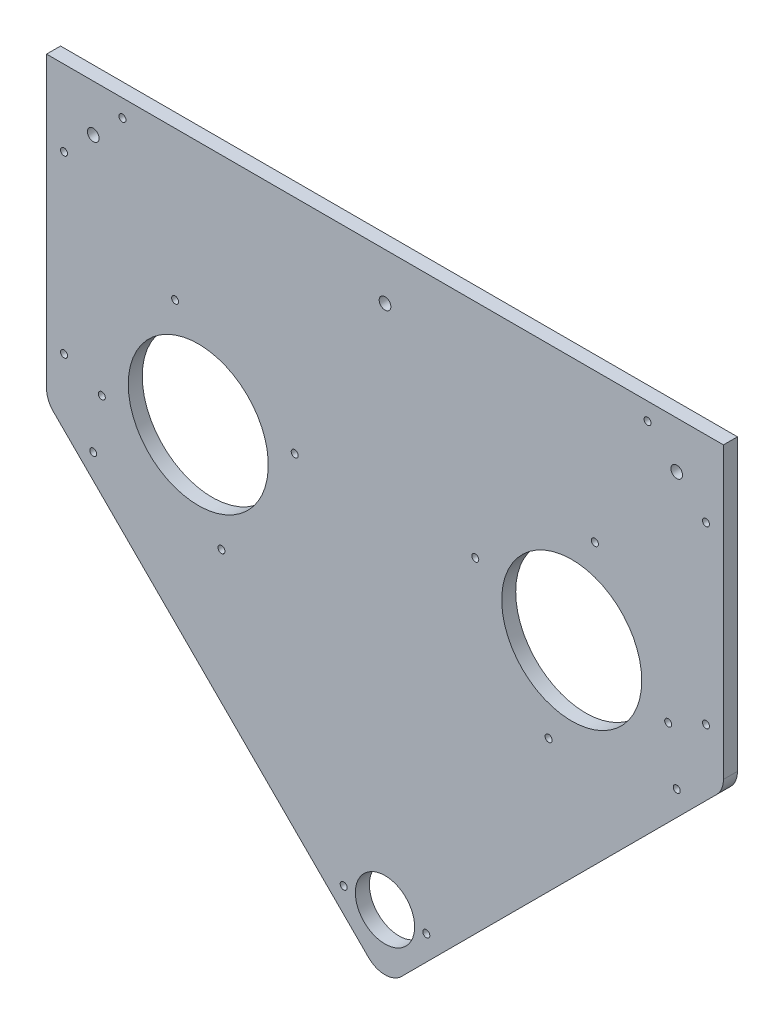
SolidWorks part; units mm, degrees
ref_plane "Front Plane" through (0, 0, 0) normal (0, 0, 1) x (1, 0, 0)
ref_plane "Top Plane" through (0, 0, 0) normal (0, 1, 0) x (1, 0, 0)
ref_plane "Right Plane" through (0, 0, 0) normal (1, 0, 0) x (0, 0, -1)
sketch "Sketch1" plane through (0, 0, 0) normal (0, 0, 1) x (1, 0, 0)
  line L0 (-125, 100) -> (125, 100) construction
  line L1 (-125, 0) -> (125, 0) construction
  line L2 (-137.5158, 87.4842) -> (-125, 100) construction
  line L3 (0, -125) -> (-125, 0) construction
  line L4 (0, -125) -> (-17.7, -125) construction
  line L5 (-125, -17.7) -> (-125, 0) construction
  line L6 (0, -125) -> (0, 100) construction
  line L7 (-145, 120) -> (145, 120)
  line L8 (145, 120) -> (145, -8.2843)
  line L9 (145, -8.2843) -> (0, -153.2843)
  line L10 (0, -153.2843) -> (-145, -8.2843)
  line L11 (-145, -8.2843) -> (-145, 120)
  circle A0 centre (-125, 100) radius 12.7 construction
  circle A1 centre (125, 100) radius 12.7 construction
  circle A4 centre (0, -125) radius 12.7
  circle A5 centre (-137.5158, 87.4842) radius 1.5
  circle A6 centre (-112.4842, 112.5158) radius 1.5
  circle A7 centre (-137.5158, 12.5158) radius 1.5
  circle A8 centre (-125, -17.7) radius 1.5
  circle A9 centre (-17.7, -125) radius 1.5
  circle A10 centre (-125, 0) radius 12.7 construction
  circle A11 centre (125, 0) radius 12.7 construction
  circle A12 centre (-125, 0) radius 17.7 construction
  circle A13 centre (-125, 100) radius 17.7 construction
  circle A14 centre (0, -125) radius 17.7 construction
  circle A15 centre (17.7, -125) radius 1.5
  circle A16 centre (125, -17.7) radius 1.5
  circle A17 centre (137.5158, 12.5158) radius 1.5
  circle A18 centre (137.5158, 87.4842) radius 1.5
  circle A19 centre (112.4842, 112.5158) radius 1.5
  circle A20 centre (0, 100) radius 2.5
  circle A21 centre (-125, 100) radius 2.5
  circle A22 centre (125, 100) radius 2.5
  point P12 (0, 100)
  point P45 (0, 120)
  dimension "D1" = 25.4
  dimension "D5" = 3
  dimension "D2" = 5
  dimension "D4" = 100
  dimension "D6" = 5
  dimension "D7" = 135
  dimension "D8" = 45
  dimension "D9" = 250
  dimension "D10" = 45
  dimension "D11" = 20
  dimension "D12" = 20
  dimension "D13" = 20
  dimension "D14" = 20
  dimension "D15" = 20
  dimension "D3" = 125
extrude "Boss-Extrude1" add sketch "Sketch1" along normal blind 6
fillet "Fillet1" radius 10 3 edges at (-145, -8.2843, 3) (145, -8.2843, 3) (0, -153.2843, 3)
sketch "Sketch2" plane through (0, 0, 6) normal (0, 0, 1) x (1, 0, 0)
  line L0 (121.326, 5.0796) -> (38.674, 24.9204) construction
  line L1 (70.0796, -26.326) -> (89.9204, 56.326) construction
  line L2 (0, 0) -> (0, 100) construction
  line L3 (145, 120) -> (-145, 120) construction
  line L4 (-145, 120) -> (-145, -4.1421) construction
  circle A0 centre (80, 15) radius 42.5 construction
  circle A1 centre (38.674, 24.9204) radius 1.5
  circle A2 centre (89.9204, 56.326) radius 1.5
  circle A3 centre (121.326, 5.0796) radius 1.5
  circle A4 centre (70.0796, -26.326) radius 1.5
  circle A5 centre (80, 15) radius 30
  circle A6 centre (-38.674, 24.9204) radius 1.5
  circle A7 centre (-89.9204, 56.326) radius 1.5
  circle A8 centre (-70.0796, -26.326) radius 1.5
  circle A9 centre (-121.326, 5.0796) radius 1.5
  circle A10 centre (-80, 15) radius 42.5 construction
  circle A11 centre (-80, 15) radius 30
  circle A12 centre (-80, 15) radius 47.5 construction
  circle A13 centre (-137.5158, 12.5158) radius 3 construction
  circle A14 centre (-125, -17.7) radius 3 construction
  point P6 (80, 15)
  point P27 (-80, 15)
  dimension "D1" = 85
  dimension "D2" = 3
  dimension "D3" = 60
  dimension "D4" = 95
  dimension "D5" = 6
  dimension "D6" = 105
  dimension "D7" = 65
extrude "Cut-Extrude1" cut sketch "Sketch2" against normal blind 10
equation "\"D1@Sketch1\" = \"cf_tube_outer_diameter\""
equation "\"D9@Sketch1\"= \"mid_plate_horizontal_spacing\""
equation "\"mid_plate_mid_to_top\" = 100mm"
equation "\"mid_plate_mid_to_bottom\" = 125mm"
equation "\"mid_plate_horizontal_spacing\" = 250mm"
equation "\"cf_tube_outer_diameter\" = 25.4mm"
equation "\"D4@Sketch1\"=\"mid_plate_mid_to_top\""
equation "\"D3@Sketch1\"=\"mid_plate_mid_to_bottom\""
